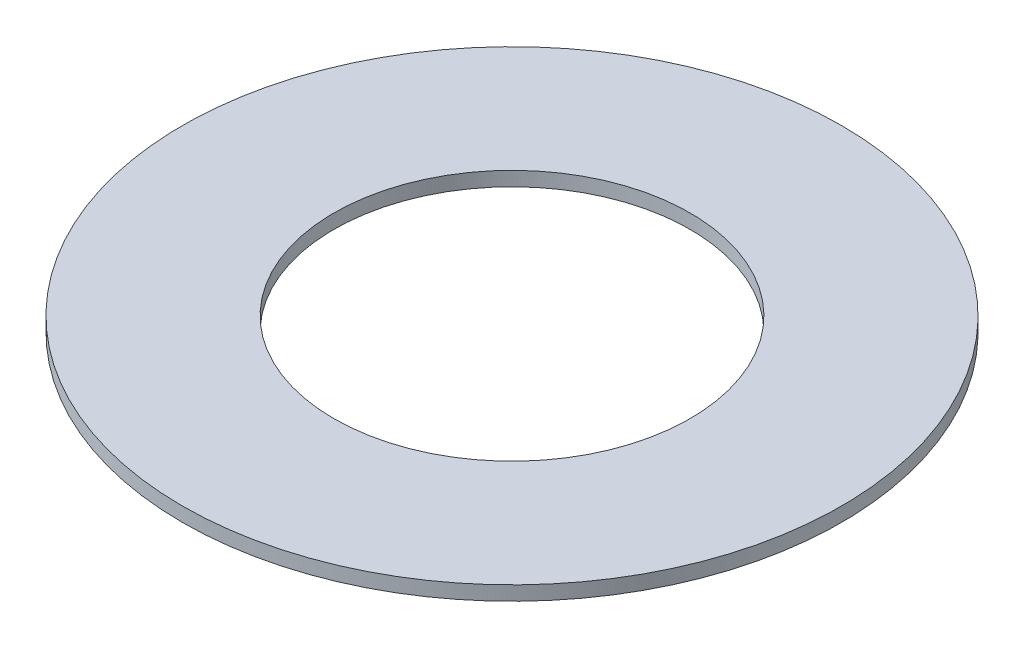
SolidWorks part; units mm, degrees
ref_plane "Front Plane" through (0, 0, 0) normal (0, 0, 1) x (1, 0, 0)
ref_plane "Top Plane" through (0, 0, 0) normal (0, 1, 0) x (1, 0, 0)
ref_plane "Right Plane" through (0, 0, 0) normal (1, 0, 0) x (0, 0, -1)
sketch "Sketch1" plane through (0, 0, 0) normal (0, 1, 0) x (1, 0, 0)
  circle A0 centre (0, 0) radius 92.5
  dimension "FLANGE_OD" = 185
extrude "Boss-Extrude1" add sketch "Sketch1" along normal blind 4
sketch "Sketch2" plane through (0, 0, 0) normal (0, 1, 0) x (1, 0, 0)
  circle A0 centre (0, 0) radius 50
  dimension "BORE_D" = 100
extrude "Cut-Extrude1" cut sketch "Sketch2" along normal through all
sketch "Sketch3" plane through (0, 4, 0) normal (0, 1, 0) x (1, 0, 0)
  circle A0 centre (0, 0) radius 27.1308 construction
  circle A1 centre (-27.1308, 0) radius 3.1297
  dimension "BOLT_D" = 6.2595
  dimension "BOLT_PCD" = 54.2616
extrude "Cut-Extrude2" cut sketch "Sketch3" against normal blind 3.8846 rebuild error yes
pattern_circular "CirPattern1" count 4 over 360 rebuild error yes
